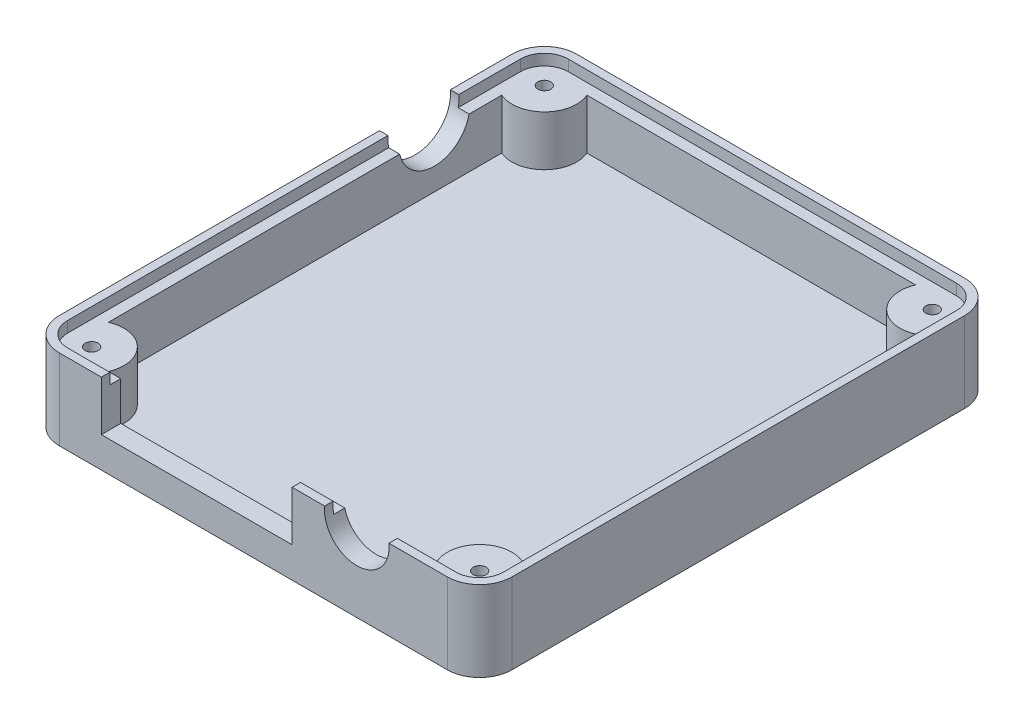
SolidWorks part; units mm, degrees
ref_plane "Front Plane" through (0, 0, 0) normal (0, 0, 1) x (1, 0, 0)
ref_plane "Top Plane" through (0, 0, 0) normal (0, 1, 0) x (1, 0, 0)
ref_plane "Right Plane" through (0, 0, 0) normal (1, 0, 0) x (0, 0, -1)
sketch "Sketch1" plane through (0, 0, 0) normal (0, 1, 0) x (1, 0, 0)
  line L1 (35, -40) -> (-35, -40)
  line L2 (35, -40) -> (35, 40)
  line L3 (35, 40) -> (-35, 40)
  line L4 (-35, -40) -> (-35, 40)
  line L5 (35, -40) -> (-35, 40) construction
  line L6 (35, 40) -> (-35, -40) construction
  point P0 (0, 0)
  dimension "D1" = 70
  dimension "D2" = 80
extrude "Boss-Extrude1" add sketch "Sketch1" along normal blind 21.5
fillet "Fillet1" radius 5 4 edges at (-35, 10.75, -40) (35, 10.75, 40) (-35, 10.75, 40) (35, 10.75, -40)
shell "Shell1" thickness 3
sketch "Sketch3" plane through (0, 21.5, 0) normal (0, 1, 0) x (1, 0, 0)
  circle A0 centre (-30, 35) radius 5
  circle A1 centre (30, 35) radius 5
  circle A2 centre (30, -35) radius 5
  circle A3 centre (-30, -35) radius 5
  arc A4 (-30, 40) -> (-35, 35) centre (-30, 35) ccw construction
  arc A5 (35, 35) -> (30, 40) centre (30, 35) ccw construction
  arc A6 (30, -40) -> (35, -35) centre (30, -35) ccw construction
  arc A7 (-35, -35) -> (-30, -40) centre (-30, -35) ccw construction
extrude "Boss-Extrude2" add sketch "Sketch3" against normal through all
sketch "Sketch2" plane through (0, 0, 0) normal (1, 0, 0) x (0, 0, -1)
  line L0 (-40, 10.75) -> (51.5624, 10.75)
  line L1 (-40, 0) -> (-40, 21.5) construction
split "Split2" trim tools "Sketch2" bodies to split 104 resulting bodies 105 106
sketch "Sketch4" plane through (0, 21.5, 0) normal (0, 1, 0) x (1, 0, 0)
  circle A0 centre (-30, 35) radius 1
  circle A1 centre (30, 35) radius 1
  circle A2 centre (30, -35) radius 1
  circle A3 centre (-30, -35) radius 1
  dimension "D1" = 2
extrude "Cut-Extrude1" cut sketch "Sketch4" against normal through all
sketch "Sketch5" plane through (0, 21.5, 0) normal (0, 1, 0) x (1, 0, 0)
  circle A0 centre (-30, 35) radius 3
  circle A1 centre (30, 35) radius 3
  circle A2 centre (30, -35) radius 3
  circle A3 centre (-30, -35) radius 3
  dimension "D1" = 6
extrude "Cut-Extrude2" cut sketch "Sketch5" against normal offset from surface (7.75 mm away) 3 up to face at (-30, 10.75, -36)
sketch "Sketch6" plane through (0, 10.75, 0) normal (0, -1, 0) x (1, 0, 0)
  line L8 (-30, -38.5) -> (30, -38.5)
  line L9 (33.5, -35) -> (33.5, 35)
  line L10 (30, 38.5) -> (-30, 38.5)
  line L11 (-33.5, 35) -> (-33.5, -35)
  line L12 (-30, -38.5) -> (30, -38.5)
  line L13 (33.5, -35) -> (33.5, 35)
  line L14 (30, 38.5) -> (-30, 38.5)
  line L15 (-33.5, 35) -> (-33.5, -35)
  arc A8 (-33.5, -35) -> (-30, -38.5) centre (-30, -35) ccw
  arc A9 (30, -38.5) -> (33.5, -35) centre (30, -35) ccw
  arc A10 (33.5, 35) -> (30, 38.5) centre (30, 35) ccw
  arc A11 (-30, 38.5) -> (-33.5, 35) centre (-30, 35) ccw
  arc A12 (-33.5, -35) -> (-30, -38.5) centre (-30, -35) ccw
  arc A13 (30, -38.5) -> (33.5, -35) centre (30, -35) ccw
  arc A14 (33.5, 35) -> (30, 38.5) centre (30, 35) ccw
  arc A15 (-30, 38.5) -> (-33.5, 35) centre (-30, 35) ccw
  dimension "D1" = 1.5
extrude "Cut-Extrude3" cut sketch "Sketch6" against normal blind 2 flip side to cut
sketch "Sketch7" plane through (0, 10.75, 0) normal (0, 1, 0) x (1, 0, 0)
  line L0 (-30, 40) -> (30, 40) construction
  line L1 (35, 35) -> (35, -35) construction
  line L2 (30, -40) -> (-30, -40) construction
  line L3 (-35, -35) -> (-35, 35) construction
  line L4 (-30, 40) -> (30, 40)
  line L5 (35, 35) -> (35, -35)
  line L6 (30, -40) -> (-30, -40)
  line L7 (-35, -35) -> (-35, 35)
  line L16 (30, 38.7) -> (-30, 38.7)
  line L17 (33.7, -35) -> (33.7, 35)
  line L18 (-30, -38.7) -> (30, -38.7)
  line L19 (-33.7, 35) -> (-33.7, -35)
  line L20 (30, 38.7) -> (-30, 38.7)
  line L21 (33.7, -35) -> (33.7, 35)
  line L22 (-30, -38.7) -> (30, -38.7)
  line L23 (-33.7, 35) -> (-33.7, -35)
  arc A0 (-30, 40) -> (-35, 35) centre (-30, 35) ccw construction
  arc A1 (35, 35) -> (30, 40) centre (30, 35) ccw construction
  arc A2 (30, -40) -> (35, -35) centre (30, -35) ccw construction
  arc A3 (-35, -35) -> (-30, -40) centre (-30, -35) ccw construction
  arc A4 (-30, 40) -> (-35, 35) centre (-30, 35) ccw
  arc A5 (35, 35) -> (30, 40) centre (30, 35) ccw
  arc A6 (30, -40) -> (35, -35) centre (30, -35) ccw
  arc A7 (-35, -35) -> (-30, -40) centre (-30, -35) ccw
  arc A16 (-30, 38.7) -> (-33.7, 35) centre (-30, 35) ccw
  arc A17 (33.7, 35) -> (30, 38.7) centre (30, 35) ccw
  arc A18 (30, -38.7) -> (33.7, -35) centre (30, -35) ccw
  arc A19 (-33.7, -35) -> (-30, -38.7) centre (-30, -35) ccw
  arc A20 (-30, 38.7) -> (-33.7, 35) centre (-30, 35) ccw
  arc A21 (33.7, 35) -> (30, 38.7) centre (30, 35) ccw
  arc A22 (30, -38.7) -> (33.7, -35) centre (30, -35) ccw
  arc A23 (-33.7, -35) -> (-30, -38.7) centre (-30, -35) ccw
  dimension "D1" = 0.2
extrude "Boss-Extrude3" add sketch "Sketch7" along normal offset from surface (1.7 mm away) 0.3 up to face at (0, 12.75, 0)
sketch "Sketch8" plane through (-35, 0, 0) normal (-1, 0, 0) x (0, 0, 1)
  line L1 (35, 12.45) -> (-35, 12.45) construction
  circle A0 centre (-20, 11.95) radius 5.5
  point P2 (-20, 11.1581)
  point P4 (0, 0)
  dimension "D1" = 20
  dimension "D2" = 11
  dimension "D3" = 0.5
extrude "Cut-Extrude4" cut sketch "Sketch8" against normal blind 10
sketch "Sketch9" plane through (0, 0, 40) normal (0, 0, 1) x (1, 0, 0)
  line L0 (30, 12.45) -> (-30, 12.45) construction
  line L1 (-20, 16.75) -> (0, 16.75)
  line L2 (-20, 16.75) -> (-20, 4.75)
  line L3 (-20, 4.75) -> (0, 4.75)
  line L4 (0, 16.75) -> (0, 4.75)
  line L5 (-10, 4.75) -> (-10, -9.1876) construction
  line L6 (-30, 21.5) -> (-30, 0) construction
  line L7 (-30, 10.75) -> (0, 10.75) construction
  circle A0 centre (16, 11.95) radius 5
  point P17 (0, 0)
  dimension "D1" = 10
  dimension "D2" = 0.5
  dimension "D3" = 16
  dimension "D4" = 20
  dimension "D5" = 12
  dimension "D6" = 10
extrude "Cut-Extrude5" cut sketch "Sketch9" against normal blind 10
sketch "Sketch11" plane through (0, 18.5, 0) normal (0, -1, 0) x (1, 0, 0)
  line L0 (-20, 38.5) -> (-30, 38.5) construction
  line L1 (-28, 38.5) -> (10.5, 38.5)
  line L2 (-28, 38.5) -> (-28, 32)
  line L3 (-28, 32) -> (-23.5, 32)
  line L4 (10.5, 38.5) -> (10.5, 32)
  line L5 (6, 32) -> (10.5, 32)
  line L6 (-25, 37) -> (7.5, 37)
  line L7 (-25, 37) -> (-25, 35)
  line L8 (-25, 35) -> (-23.5, 35)
  line L9 (7.5, 37) -> (7.5, 35)
  line L11 (-23.5, 35) -> (-23.5, 32)
  line L13 (6, 35) -> (6, 32)
  line L14 (6, 35) -> (7.5, 35)
  line L15 (-25.4174, 37) -> (25.4174, 37) construction
  arc A1 (-32, 30.4174) -> (-25.4174, 37) centre (-30, 35) ccw construction
  dimension "D1" = 2
  dimension "D2" = 32.5
  dimension "D3" = 1.5
  dimension "D4" = 1.5
  dimension "D5" = 3
  dimension "D6" = 3
  dimension "D7" = 3
extrude "Boss-Extrude4" add sketch "Sketch11" along normal up to surface (7.75 mm away) up to face at (-28.1123, 10.75, 23.2041)
sketch "Sketch12" plane through (0, 0, 37) normal (0, 0, -1) x (-1, 0, 0)
  line L0 (23.5, 10.75) -> (23.5, 18.5) construction
  line L1 (23.5, 4.75) -> (-6, 4.75)
  line L2 (23.5, 4.75) -> (23.5, 16.75)
  line L3 (23.5, 16.75) -> (-6, 16.75)
  line L4 (-6, 4.75) -> (-6, 16.75)
  line L5 (-6, 10.75) -> (-6, 18.5) construction
  line L6 (0, 16.75) -> (20, 16.75) construction
  line L7 (0, 4.75) -> (20, 4.75) construction
extrude "Cut-Extrude6" cut sketch "Sketch12" against normal blind 10
sketch "Sketch14" plane through (0, 10.75, 0) normal (0, -1, 0) x (1, 0, 0)
  line L2 (11.1461, 36.8) -> (6, 36.8)
  line L3 (10.5, 36.8) -> (7.5, 36.8)
  line L10 (6, 38.5) -> (6, 37)
  line L11 (6, 37) -> (7.5, 37)
  line L12 (7.5, 37) -> (7.5, 35)
  line L13 (7.5, 35) -> (6, 35)
  line L14 (6, 35) -> (6, 32)
  line L15 (6, 32) -> (10.5, 32)
  line L16 (10.5, 32) -> (10.5, 37)
  line L17 (10.5, 37) -> (11.1461, 37)
  line L18 (11.1461, 37) -> (11.1461, 38.5)
  line L19 (11.1461, 38.5) -> (6, 38.5)
  line L22 (7.5, 36.8) -> (7.5, 35)
  line L23 (7.5, 35) -> (6, 35)
  line L24 (6, 35) -> (6, 32)
  line L25 (6, 32) -> (10.5, 32)
  line L26 (10.5, 32) -> (10.5, 36.8)
  dimension "D2" = 0.2
  dimension "D1" = 0
extrude "Boss-Extrude5" add sketch "Sketch14" along normal blind 5
delete or keep bodies "Body-Delete/Keep 1" type keep bodies bodies 119
